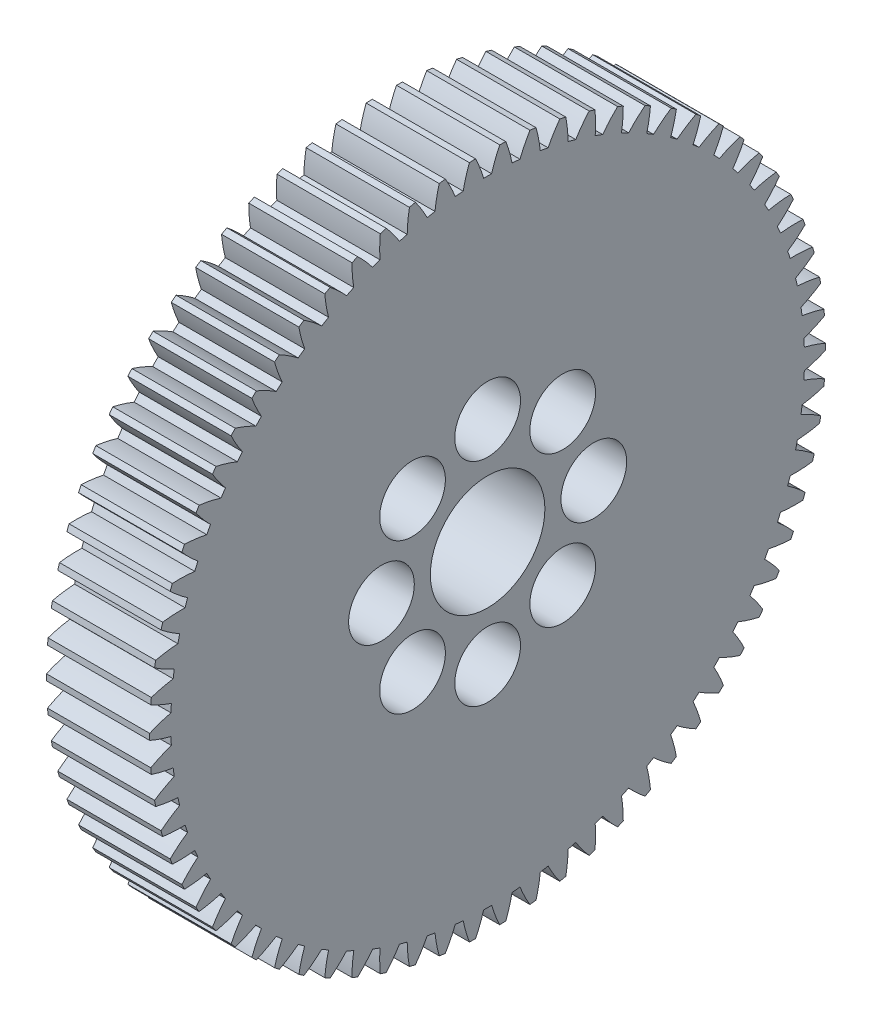
SolidWorks part; units mm, degrees
ref_plane "正面" through (0, 0, 0) normal (0, 0, 1) x (1, 0, 0)
ref_plane "平面" through (0, 0, 0) normal (0, 1, 0) x (1, 0, 0)
ref_plane "右側面" through (0, 0, 0) normal (1, 0, 0) x (0, 0, -1)
ref_plane "Plane1" through (10.108, 0, 0) normal (1, 0, 0) x (0, 0, -1)
sketch "Sketch1" plane through (10.108, 0, 0) normal (1, 0, 0) x (0, 0, -1)
  circle A0 centre (0, -2.0042) radius 4
  arc A1 (-32.5754, 13.3205) -> (-30.8638, 11.6495) centre (-21.9753, 22.466) ccw
  arc A2 (-30.8638, 11.6495) -> (-31.1976, 10.8685) centre (0, -2.0042) ccw
  arc A3 (-31.1976, 10.8685) -> (-33.5882, 10.9508) centre (-32.8732, -3.0309) ccw
  arc A4 (-33.5882, 10.9508) -> (-33.8179, 10.3388) centre (0, -2.0042) ccw
  arc A5 (-33.8179, 10.3388) -> (-31.9634, 8.8279) centre (-24.0803, 20.3976) ccw
  arc A6 (-31.9634, 8.8279) -> (-32.2259, 8.0201) centre (0, -2.0042) ccw
  arc A7 (-32.2259, 8.0201) -> (-34.6143, 7.8879) centre (-32.6488, -5.9735) ccw
  arc A8 (-34.6143, 7.8879) -> (-34.7882, 7.2577) centre (0, -2.0042) ccw
  arc A9 (-34.7882, 7.2577) -> (-32.8057, 5.9191) centre (-25.9915, 18.1489) ccw
  arc A10 (-32.8057, 5.9191) -> (-32.9947, 5.0911) centre (0, -2.0042) ccw
  arc A11 (-32.9947, 5.0911) -> (-35.3616, 4.7452) centre (-32.1616, -8.8841) ccw
  arc A12 (-35.3616, 4.7452) -> (-35.4784, 4.102) centre (0, -2.0042) ccw
  arc A13 (-35.4784, 4.102) -> (-33.3839, 2.9466) centre (-27.6934, 15.7379) ccw
  arc A14 (-33.3839, 2.9466) -> (-33.4979, 2.1049) centre (0, -2.0042) ccw
  arc A15 (-33.4979, 2.1049) -> (-35.8243, 1.5483) centre (-31.4154, -11.7394) ccw
  arc A16 (-35.8243, 1.5483) -> (-35.8829, 0.8972) centre (0, -2.0042) ccw
  arc A17 (-35.8829, 0.8972) -> (-33.6933, -0.0659) centre (-29.1723, 13.184) ccw
  arc A18 (-33.6933, -0.0659) -> (-33.7314, -0.9144) centre (0, -2.0042) ccw
  arc A19 (-33.7314, -0.9144) -> (-35.9985, -1.6773) centre (-30.4163, -14.5162) ccw
  arc A20 (-35.9985, -1.6773) -> (-35.9985, -2.331) centre (0, -2.0042) ccw
  arc A21 (-35.9985, -2.331) -> (-33.7314, -3.0939) centre (-30.4163, 10.5079) ccw
  arc A22 (-33.7314, -3.0939) -> (-33.6933, -3.9425) centre (0, -2.0042) ccw
  arc A23 (-33.6933, -3.9425) -> (-35.8829, -4.9055) centre (-29.1723, -17.1924) ccw
  arc A24 (-35.8829, -4.9055) -> (-35.8243, -5.5566) centre (0, -2.0042) ccw
  arc A25 (-35.8243, -5.5566) -> (-33.4979, -6.1132) centre (-31.4154, 7.7311) ccw
  arc A26 (-33.4979, -6.1132) -> (-33.3839, -6.9549) centre (0, -2.0042) ccw
  arc A27 (-33.3839, -6.9549) -> (-35.4784, -8.1103) centre (-27.6934, -19.7462) ccw
  arc A28 (-35.4784, -8.1103) -> (-35.3616, -8.7536) centre (0, -2.0042) ccw
  arc A29 (-35.3616, -8.7536) -> (-32.9947, -9.0994) centre (-32.1616, 4.8758) ccw
  arc A30 (-32.9947, -9.0994) -> (-32.8057, -9.9275) centre (0, -2.0042) ccw
  arc A31 (-32.8057, -9.9275) -> (-34.7882, -11.266) centre (-25.9915, -22.1572) ccw
  arc A32 (-34.7882, -11.266) -> (-34.6143, -11.8962) centre (0, -2.0042) ccw
  arc A33 (-34.6143, -11.8962) -> (-32.2259, -12.0284) centre (-32.6488, 1.9652) ccw
  arc A34 (-32.2259, -12.0284) -> (-31.9634, -12.8363) centre (0, -2.0042) ccw
  arc A35 (-31.9634, -12.8363) -> (-33.8179, -14.3471) centre (-24.0803, -24.4059) ccw
  arc A36 (-33.8179, -14.3471) -> (-33.5882, -14.9592) centre (0, -2.0042) ccw
  arc A37 (-33.5882, -14.9592) -> (-31.1976, -14.8768) centre (-32.8732, -0.9774) ccw
  arc A38 (-31.1976, -14.8768) -> (-30.8638, -15.6578) centre (0, -2.0042) ccw
  arc A39 (-30.8638, -15.6578) -> (-32.5754, -17.3288) centre (-21.9753, -26.4743) ccw
  arc A40 (-32.5754, -17.3288) -> (-32.2917, -17.9178) centre (0, -2.0042) ccw
  arc A41 (-32.2917, -17.9178) -> (-29.9181, -17.6215) centre (-32.8329, -3.9283) ccw
  arc A42 (-29.9181, -17.6215) -> (-29.5156, -18.3695) centre (0, -2.0042) ccw
  arc A43 (-29.5156, -18.3695) -> (-31.0705, -20.1872) centre (-19.6934, -28.3456) ccw
  arc A44 (-31.0705, -20.1872) -> (-30.7352, -20.7484) centre (0, -2.0042) ccw
  arc A45 (-30.7352, -20.7484) -> (-28.3977, -20.2405) centre (-32.5283, -6.8637) ccw
  arc A46 (-28.3977, -20.2405) -> (-27.9298, -20.9494) centre (0, -2.0042) ccw
  arc A47 (-27.9298, -20.9494) -> (-29.3155, -22.8991) centre (-17.2529, -30.0049) ccw
  arc A48 (-29.3155, -22.8991) -> (-28.9313, -23.428) centre (0, -2.0042) ccw
  arc A49 (-28.9313, -23.428) -> (-26.6487, -22.7126) centre (-31.9617, -9.7599) ccw
  arc A50 (-26.6487, -22.7126) -> (-26.1191, -23.3767) centre (0, -2.0042) ccw
  arc A51 (-26.1191, -23.3767) -> (-27.3245, -25.4428) centre (-14.6734, -31.4387) ccw
  arc A52 (-27.3245, -25.4428) -> (-26.8944, -25.9351) centre (0, -2.0042) ccw
  arc A53 (-26.8944, -25.9351) -> (-24.6852, -25.018) centre (-31.1378, -12.5937) ccw
  arc A54 (-24.6852, -25.018) -> (-24.0982, -25.632) centre (0, -2.0042) ccw
  arc A55 (-24.0982, -25.632) -> (-25.1135, -27.7978) centre (-11.9759, -32.6355) ccw
  arc A56 (-25.1135, -27.7978) -> (-24.641, -28.2496) centre (0, -2.0042) ccw
  arc A57 (-24.641, -28.2496) -> (-22.5228, -27.1381) centre (-30.0632, -15.3423) ccw
  arc A58 (-22.5228, -27.1381) -> (-21.8832, -27.697) centre (0, -2.0042) ccw
  arc A59 (-21.8832, -27.697) -> (-22.7003, -29.9451) centre (-9.1819, -33.5857) ccw
  arc A60 (-22.7003, -29.9451) -> (-22.1892, -30.3527) centre (0, -2.0042) ccw
  arc A61 (-22.1892, -30.3527) -> (-20.1792, -29.0559) centre (-28.7466, -17.9834) ccw
  arc A62 (-20.1792, -29.0559) -> (-19.492, -29.5551) centre (0, -2.0042) ccw
  arc A63 (-19.492, -29.5551) -> (-20.1043, -31.8675) centre (-6.314, -34.2816) ccw
  arc A64 (-20.1043, -31.8675) -> (-19.5587, -32.2276) centre (0, -2.0042) ccw
  arc A65 (-19.5587, -32.2276) -> (-17.673, -30.7558) centre (-27.1985, -20.4959) ccw
  arc A66 (-17.673, -30.7558) -> (-16.9439, -31.1915) centre (0, -2.0042) ccw
  arc A67 (-16.9439, -31.1915) -> (-17.3464, -33.5494) centre (-3.3952, -34.7177) ccw
  arc A68 (-17.3464, -33.5494) -> (-16.7707, -33.8592) centre (0, -2.0042) ccw
  arc A69 (-16.7707, -33.8592) -> (-15.0246, -32.2243) centre (-25.4314, -22.8595) ccw
  arc A70 (-15.0246, -32.2243) -> (-14.2593, -32.5928) centre (0, -2.0042) ccw
  arc A71 (-14.2593, -32.5928) -> (-14.4489, -34.9773) centre (-0.4492, -34.8903) ccw
  arc A72 (-14.4489, -34.9773) -> (-13.8478, -35.2343) centre (0, -2.0042) ccw
  arc A73 (-13.8478, -35.2343) -> (-12.2552, -33.4494) centre (-23.4596, -25.0552) ccw
  arc A74 (-12.2552, -33.4494) -> (-11.46, -33.7479) centre (0, -2.0042) ccw
  arc A75 (-11.46, -33.7479) -> (-11.435, -36.1398) centre (2.5006, -34.7982) ccw
  arc A76 (-11.435, -36.1398) -> (-10.8133, -36.3418) centre (0, -2.0042) ccw
  arc A77 (-10.8133, -36.3418) -> (-9.3872, -34.4214) centre (-21.2988, -27.0653) ccw
  arc A78 (-9.3872, -34.4214) -> (-8.5684, -34.6474) centre (0, -2.0042) ccw
  arc A79 (-8.5684, -34.6474) -> (-8.3291, -37.0274) centre (5.4301, -34.442) ccw
  arc A80 (-8.3291, -37.0274) -> (-7.6918, -37.1729) centre (0, -2.0042) ccw
  arc A81 (-7.6918, -37.1729) -> (-6.4435, -35.1323) centre (-18.9666, -28.8736) ccw
  arc A82 (-6.4435, -35.1323) -> (-5.6078, -35.284) centre (0, -2.0042) ccw
  arc A83 (-5.6078, -35.284) -> (-5.1561, -37.633) centre (8.316, -33.8247) ccw
  arc A84 (-5.1561, -37.633) -> (-4.5083, -37.7208) centre (0, -2.0042) ccw
  arc A85 (-4.5083, -37.7208) -> (-3.448, -35.5766) centre (-16.4817, -30.4656) ccw
  arc A86 (-3.448, -35.5766) -> (-2.602, -35.6527) centre (0, -2.0042) ccw
  arc A87 (-2.602, -35.6527) -> (-1.9416, -37.9518) centre (11.1349, -32.9512) ccw
  arc A88 (-1.9416, -37.9518) -> (-1.2885, -37.9811) centre (0, -2.0042) ccw
  arc A89 (-1.2885, -37.9811) -> (-0.4247, -35.7505) centre (-13.8641, -31.8285) ccw
  arc A90 (-0.4247, -35.7505) -> (0.4247, -35.7505) centre (0, -2.0042) ccw
  arc A91 (0.4247, -35.7505) -> (1.2885, -37.9811) centre (13.8641, -31.8285) ccw
  arc A92 (1.2885, -37.9811) -> (1.9416, -37.9518) centre (0, -2.0042) ccw
  arc A93 (1.9416, -37.9518) -> (2.602, -35.6527) centre (-11.1349, -32.9512) ccw
  arc A94 (2.602, -35.6527) -> (3.448, -35.5766) centre (0, -2.0042) ccw
  arc A95 (3.448, -35.5766) -> (4.5083, -37.7208) centre (16.4817, -30.4656) ccw
  arc A96 (4.5083, -37.7208) -> (5.1561, -37.633) centre (0, -2.0042) ccw
  arc A97 (5.1561, -37.633) -> (5.6078, -35.284) centre (-8.316, -33.8247) ccw
  arc A98 (5.6078, -35.284) -> (6.4435, -35.1323) centre (0, -2.0042) ccw
  arc A99 (6.4435, -35.1323) -> (7.6918, -37.1729) centre (18.9666, -28.8736) ccw
  arc A100 (7.6918, -37.1729) -> (8.3291, -37.0274) centre (0, -2.0042) ccw
  arc A101 (8.3291, -37.0274) -> (8.5684, -34.6474) centre (-5.4301, -34.442) ccw
  arc A102 (8.5684, -34.6474) -> (9.3872, -34.4214) centre (0, -2.0042) ccw
  arc A103 (9.3872, -34.4214) -> (10.8133, -36.3418) centre (21.2988, -27.0653) ccw
  arc A104 (10.8133, -36.3418) -> (11.435, -36.1398) centre (0, -2.0042) ccw
  arc A105 (11.435, -36.1398) -> (11.46, -33.7479) centre (-2.5006, -34.7982) ccw
  arc A106 (11.46, -33.7479) -> (12.2552, -33.4494) centre (0, -2.0042) ccw
  arc A107 (12.2552, -33.4494) -> (13.8478, -35.2343) centre (23.4596, -25.0552) ccw
  arc A108 (13.8478, -35.2343) -> (14.4489, -34.9773) centre (0, -2.0042) ccw
  arc A109 (14.4489, -34.9773) -> (14.2593, -32.5928) centre (0.4492, -34.8903) ccw
  arc A110 (14.2593, -32.5928) -> (15.0246, -32.2243) centre (0, -2.0042) ccw
  arc A111 (15.0246, -32.2243) -> (16.7707, -33.8592) centre (25.4314, -22.8595) ccw
  arc A112 (16.7707, -33.8592) -> (17.3464, -33.5494) centre (0, -2.0042) ccw
  arc A113 (17.3464, -33.5494) -> (16.9439, -31.1915) centre (3.3952, -34.7177) ccw
  arc A114 (16.9439, -31.1915) -> (17.673, -30.7558) centre (0, -2.0042) ccw
  arc A115 (17.673, -30.7558) -> (19.5587, -32.2276) centre (27.1985, -20.4959) ccw
  arc A116 (19.5587, -32.2276) -> (20.1043, -31.8675) centre (0, -2.0042) ccw
  arc A117 (20.1043, -31.8675) -> (19.492, -29.5551) centre (6.314, -34.2816) ccw
  arc A118 (19.492, -29.5551) -> (20.1792, -29.0559) centre (0, -2.0042) ccw
  arc A119 (20.1792, -29.0559) -> (22.1892, -30.3527) centre (28.7466, -17.9834) ccw
  arc A120 (22.1892, -30.3527) -> (22.7003, -29.9451) centre (0, -2.0042) ccw
  arc A121 (22.7003, -29.9451) -> (21.8832, -27.697) centre (9.1819, -33.5857) ccw
  arc A122 (21.8832, -27.697) -> (22.5228, -27.1381) centre (0, -2.0042) ccw
  arc A123 (22.5228, -27.1381) -> (24.641, -28.2496) centre (30.0632, -15.3423) ccw
  arc A124 (24.641, -28.2496) -> (25.1135, -27.7978) centre (0, -2.0042) ccw
  arc A125 (25.1135, -27.7978) -> (24.0982, -25.632) centre (11.9759, -32.6355) ccw
  arc A126 (24.0982, -25.632) -> (24.6852, -25.018) centre (0, -2.0042) ccw
  arc A127 (24.6852, -25.018) -> (26.8944, -25.9351) centre (31.1378, -12.5937) ccw
  arc A128 (26.8944, -25.9351) -> (27.3245, -25.4428) centre (0, -2.0042) ccw
  arc A129 (27.3245, -25.4428) -> (26.1191, -23.3767) centre (14.6734, -31.4387) ccw
  arc A130 (26.1191, -23.3767) -> (26.6487, -22.7126) centre (0, -2.0042) ccw
  arc A131 (26.6487, -22.7126) -> (28.9313, -23.428) centre (31.9617, -9.7599) ccw
  arc A132 (28.9313, -23.428) -> (29.3155, -22.8991) centre (0, -2.0042) ccw
  arc A133 (29.3155, -22.8991) -> (27.9298, -20.9494) centre (17.2529, -30.0049) ccw
  arc A134 (27.9298, -20.9494) -> (28.3977, -20.2405) centre (0, -2.0042) ccw
  arc A135 (28.3977, -20.2405) -> (30.7352, -20.7484) centre (32.5283, -6.8637) ccw
  arc A136 (30.7352, -20.7484) -> (31.0705, -20.1872) centre (0, -2.0042) ccw
  arc A137 (31.0705, -20.1872) -> (29.5156, -18.3695) centre (19.6934, -28.3456) ccw
  arc A138 (29.5156, -18.3695) -> (29.9181, -17.6215) centre (0, -2.0042) ccw
  arc A139 (29.9181, -17.6215) -> (32.2917, -17.9178) centre (32.8329, -3.9283) ccw
  arc A140 (32.2917, -17.9178) -> (32.5754, -17.3288) centre (0, -2.0042) ccw
  arc A141 (32.5754, -17.3288) -> (30.8638, -15.6578) centre (21.9753, -26.4743) ccw
  arc A142 (30.8638, -15.6578) -> (31.1976, -14.8768) centre (0, -2.0042) ccw
  arc A143 (31.1976, -14.8768) -> (33.5882, -14.9592) centre (32.8732, -0.9774) ccw
  arc A144 (33.5882, -14.9592) -> (33.8179, -14.3471) centre (0, -2.0042) ccw
  arc A145 (33.8179, -14.3471) -> (31.9634, -12.8363) centre (24.0803, -24.4059) ccw
  arc A146 (31.9634, -12.8363) -> (32.2259, -12.0284) centre (0, -2.0042) ccw
  arc A147 (32.2259, -12.0284) -> (34.6143, -11.8962) centre (32.6488, 1.9652) ccw
  arc A148 (34.6143, -11.8962) -> (34.7882, -11.266) centre (0, -2.0042) ccw
  arc A149 (34.7882, -11.266) -> (32.8057, -9.9275) centre (25.9915, -22.1572) ccw
  arc A150 (32.8057, -9.9275) -> (32.9947, -9.0994) centre (0, -2.0042) ccw
  arc A151 (32.9947, -9.0994) -> (35.3616, -8.7536) centre (32.1616, 4.8758) ccw
  arc A152 (35.3616, -8.7536) -> (35.4784, -8.1103) centre (0, -2.0042) ccw
  arc A153 (35.4784, -8.1103) -> (33.3839, -6.9549) centre (27.6934, -19.7462) ccw
  arc A154 (33.3839, -6.9549) -> (33.4979, -6.1132) centre (0, -2.0042) ccw
  arc A155 (33.4979, -6.1132) -> (35.8243, -5.5566) centre (31.4154, 7.7311) ccw
  arc A156 (35.8243, -5.5566) -> (35.8829, -4.9055) centre (0, -2.0042) ccw
  arc A157 (35.8829, -4.9055) -> (33.6933, -3.9425) centre (29.1723, -17.1924) ccw
  arc A158 (33.6933, -3.9425) -> (33.7314, -3.0939) centre (0, -2.0042) ccw
  arc A159 (33.7314, -3.0939) -> (35.9985, -2.331) centre (30.4163, 10.5079) ccw
  arc A160 (35.9985, -2.331) -> (35.9985, -1.6773) centre (0, -2.0042) ccw
  arc A161 (35.9985, -1.6773) -> (33.7314, -0.9144) centre (30.4163, -14.5162) ccw
  arc A162 (33.7314, -0.9144) -> (33.6933, -0.0659) centre (0, -2.0042) ccw
  arc A163 (33.6933, -0.0659) -> (35.8829, 0.8972) centre (29.1723, 13.184) ccw
  arc A164 (35.8829, 0.8972) -> (35.8243, 1.5483) centre (0, -2.0042) ccw
  arc A165 (35.8243, 1.5483) -> (33.4979, 2.1049) centre (31.4154, -11.7394) ccw
  arc A166 (33.4979, 2.1049) -> (33.3839, 2.9466) centre (0, -2.0042) ccw
  arc A167 (33.3839, 2.9466) -> (35.4784, 4.102) centre (27.6934, 15.7379) ccw
  arc A168 (35.4784, 4.102) -> (35.3616, 4.7452) centre (0, -2.0042) ccw
  arc A169 (35.3616, 4.7452) -> (32.9947, 5.0911) centre (32.1616, -8.8841) ccw
  arc A170 (32.9947, 5.0911) -> (32.8057, 5.9191) centre (0, -2.0042) ccw
  arc A171 (32.8057, 5.9191) -> (34.7882, 7.2577) centre (25.9915, 18.1489) ccw
  arc A172 (34.7882, 7.2577) -> (34.6143, 7.8879) centre (0, -2.0042) ccw
  arc A173 (34.6143, 7.8879) -> (32.2259, 8.0201) centre (32.6488, -5.9735) ccw
  arc A174 (32.2259, 8.0201) -> (31.9634, 8.8279) centre (0, -2.0042) ccw
  arc A175 (31.9634, 8.8279) -> (33.8179, 10.3388) centre (24.0803, 20.3976) ccw
  arc A176 (33.8179, 10.3388) -> (33.5882, 10.9508) centre (0, -2.0042) ccw
  arc A177 (33.5882, 10.9508) -> (31.1976, 10.8685) centre (32.8732, -3.0309) ccw
  arc A178 (31.1976, 10.8685) -> (30.8638, 11.6495) centre (0, -2.0042) ccw
  arc A179 (30.8638, 11.6495) -> (32.5754, 13.3205) centre (21.9753, 22.466) ccw
  arc A180 (32.5754, 13.3205) -> (32.2917, 13.9095) centre (0, -2.0042) ccw
  arc A181 (32.2917, 13.9095) -> (29.9181, 13.6132) centre (32.8329, -0.08) ccw
  arc A182 (29.9181, 13.6132) -> (29.5156, 14.3611) centre (0, -2.0042) ccw
  arc A183 (29.5156, 14.3611) -> (31.0705, 16.1789) centre (19.6934, 24.3373) ccw
  arc A184 (31.0705, 16.1789) -> (30.7352, 16.74) centre (0, -2.0042) ccw
  arc A185 (30.7352, 16.74) -> (28.3977, 16.2321) centre (32.5283, 2.8553) ccw
  arc A186 (28.3977, 16.2321) -> (27.9298, 16.941) centre (0, -2.0042) ccw
  arc A187 (27.9298, 16.941) -> (29.3155, 18.8908) centre (17.2529, 25.9966) ccw
  arc A188 (29.3155, 18.8908) -> (28.9313, 19.4197) centre (0, -2.0042) ccw
  arc A189 (28.9313, 19.4197) -> (26.6487, 18.7043) centre (31.9617, 5.7516) ccw
  arc A190 (26.6487, 18.7043) -> (26.1191, 19.3684) centre (0, -2.0042) ccw
  arc A191 (26.1191, 19.3684) -> (27.3245, 21.4345) centre (14.6734, 27.4304) ccw
  arc A192 (27.3245, 21.4345) -> (26.8944, 21.9268) centre (0, -2.0042) ccw
  arc A193 (26.8944, 21.9268) -> (24.6852, 21.0097) centre (31.1378, 8.5854) ccw
  arc A194 (24.6852, 21.0097) -> (24.0982, 21.6236) centre (0, -2.0042) ccw
  arc A195 (24.0982, 21.6236) -> (25.1135, 23.7895) centre (11.9759, 28.6272) ccw
  arc A196 (25.1135, 23.7895) -> (24.641, 24.2413) centre (0, -2.0042) ccw
  arc A197 (24.641, 24.2413) -> (22.5228, 23.1298) centre (30.0632, 11.3339) ccw
  arc A198 (22.5228, 23.1298) -> (21.8832, 23.6887) centre (0, -2.0042) ccw
  arc A199 (21.8832, 23.6887) -> (22.7003, 25.9368) centre (9.1819, 29.5774) ccw
  arc A200 (22.7003, 25.9368) -> (22.1892, 26.3444) centre (0, -2.0042) ccw
  arc A201 (22.1892, 26.3444) -> (20.1792, 25.0476) centre (28.7466, 13.9751) ccw
  arc A202 (20.1792, 25.0476) -> (19.492, 25.5468) centre (0, -2.0042) ccw
  arc A203 (19.492, 25.5468) -> (20.1043, 27.8592) centre (6.314, 30.2733) ccw
  arc A204 (20.1043, 27.8592) -> (19.5587, 28.2193) centre (0, -2.0042) ccw
  arc A205 (19.5587, 28.2193) -> (17.673, 26.7475) centre (27.1985, 16.4876) ccw
  arc A206 (17.673, 26.7475) -> (16.9439, 27.1832) centre (0, -2.0042) ccw
  arc A207 (16.9439, 27.1832) -> (17.3464, 29.5411) centre (3.3952, 30.7094) ccw
  arc A208 (17.3464, 29.5411) -> (16.7707, 29.8509) centre (0, -2.0042) ccw
  arc A209 (16.7707, 29.8509) -> (15.0246, 28.216) centre (25.4314, 18.8512) ccw
  arc A210 (15.0246, 28.216) -> (14.2593, 28.5845) centre (0, -2.0042) ccw
  arc A211 (14.2593, 28.5845) -> (14.4489, 30.969) centre (0.4492, 30.882) ccw
  arc A212 (14.4489, 30.969) -> (13.8478, 31.2259) centre (0, -2.0042) ccw
  arc A213 (13.8478, 31.2259) -> (12.2552, 29.4411) centre (23.4596, 21.0469) ccw
  arc A214 (12.2552, 29.4411) -> (11.46, 29.7396) centre (0, -2.0042) ccw
  arc A215 (11.46, 29.7396) -> (11.435, 32.1315) centre (-2.5006, 30.7899) ccw
  arc A216 (11.435, 32.1315) -> (10.8133, 32.3335) centre (0, -2.0042) ccw
  arc A217 (10.8133, 32.3335) -> (9.3872, 30.4131) centre (21.2988, 23.057) ccw
  arc A218 (9.3872, 30.4131) -> (8.5684, 30.639) centre (0, -2.0042) ccw
  arc A219 (8.5684, 30.639) -> (8.3291, 33.0191) centre (-5.4301, 30.4337) ccw
  arc A220 (8.3291, 33.0191) -> (7.6918, 33.1645) centre (0, -2.0042) ccw
  arc A221 (7.6918, 33.1645) -> (6.4435, 31.124) centre (18.9666, 24.8653) ccw
  arc A222 (6.4435, 31.124) -> (5.6078, 31.2757) centre (0, -2.0042) ccw
  arc A223 (5.6078, 31.2757) -> (5.1561, 33.6247) centre (-8.316, 29.8164) ccw
  arc A224 (5.1561, 33.6247) -> (4.5083, 33.7124) centre (0, -2.0042) ccw
  arc A225 (4.5083, 33.7124) -> (3.448, 31.5682) centre (16.4817, 26.4573) ccw
  arc A226 (3.448, 31.5682) -> (2.602, 31.6444) centre (0, -2.0042) ccw
  arc A227 (2.602, 31.6444) -> (1.9416, 33.9434) centre (-11.1349, 28.9428) ccw
  arc A228 (1.9416, 33.9434) -> (1.2885, 33.9728) centre (0, -2.0042) ccw
  arc A229 (1.2885, 33.9728) -> (0.4247, 31.7422) centre (13.8641, 27.8201) ccw
  arc A230 (0.4247, 31.7422) -> (-0.4247, 31.7422) centre (0, -2.0042) ccw
  arc A231 (-0.4247, 31.7422) -> (-1.2885, 33.9728) centre (-13.8641, 27.8201) ccw
  arc A232 (-1.2885, 33.9728) -> (-1.9416, 33.9434) centre (0, -2.0042) ccw
  arc A233 (-1.9416, 33.9434) -> (-2.602, 31.6444) centre (11.1349, 28.9428) ccw
  arc A234 (-2.602, 31.6444) -> (-3.448, 31.5682) centre (0, -2.0042) ccw
  arc A235 (-3.448, 31.5682) -> (-4.5083, 33.7124) centre (-16.4817, 26.4573) ccw
  arc A236 (-4.5083, 33.7124) -> (-5.1561, 33.6247) centre (0, -2.0042) ccw
  arc A237 (-5.1561, 33.6247) -> (-5.6078, 31.2757) centre (8.316, 29.8164) ccw
  arc A238 (-5.6078, 31.2757) -> (-6.4435, 31.124) centre (0, -2.0042) ccw
  arc A239 (-6.4435, 31.124) -> (-7.6918, 33.1645) centre (-18.9666, 24.8653) ccw
  arc A240 (-7.6918, 33.1645) -> (-8.3291, 33.0191) centre (0, -2.0042) ccw
  arc A241 (-8.3291, 33.0191) -> (-8.5684, 30.639) centre (5.4301, 30.4337) ccw
  arc A242 (-8.5684, 30.639) -> (-9.3872, 30.4131) centre (0, -2.0042) ccw
  arc A243 (-9.3872, 30.4131) -> (-10.8133, 32.3335) centre (-21.2988, 23.057) ccw
  arc A244 (-10.8133, 32.3335) -> (-11.435, 32.1315) centre (0, -2.0042) ccw
  arc A245 (-11.435, 32.1315) -> (-11.46, 29.7396) centre (2.5006, 30.7899) ccw
  arc A246 (-11.46, 29.7396) -> (-12.2552, 29.4411) centre (0, -2.0042) ccw
  arc A247 (-12.2552, 29.4411) -> (-13.8478, 31.2259) centre (-23.4596, 21.0469) ccw
  arc A248 (-13.8478, 31.2259) -> (-14.4489, 30.969) centre (0, -2.0042) ccw
  arc A249 (-14.4489, 30.969) -> (-14.2593, 28.5845) centre (-0.4492, 30.882) ccw
  arc A250 (-14.2593, 28.5845) -> (-15.0246, 28.216) centre (0, -2.0042) ccw
  arc A251 (-15.0246, 28.216) -> (-16.7707, 29.8509) centre (-25.4314, 18.8512) ccw
  arc A252 (-16.7707, 29.8509) -> (-17.3464, 29.5411) centre (0, -2.0042) ccw
  arc A253 (-17.3464, 29.5411) -> (-16.9439, 27.1832) centre (-3.3952, 30.7094) ccw
  arc A254 (-16.9439, 27.1832) -> (-17.673, 26.7475) centre (0, -2.0042) ccw
  arc A255 (-17.673, 26.7475) -> (-19.5587, 28.2193) centre (-27.1985, 16.4876) ccw
  arc A256 (-19.5587, 28.2193) -> (-20.1043, 27.8592) centre (0, -2.0042) ccw
  arc A257 (-20.1043, 27.8592) -> (-19.492, 25.5468) centre (-6.314, 30.2733) ccw
  arc A258 (-19.492, 25.5468) -> (-20.1792, 25.0476) centre (0, -2.0042) ccw
  arc A259 (-20.1792, 25.0476) -> (-22.1892, 26.3444) centre (-28.7466, 13.9751) ccw
  arc A260 (-22.1892, 26.3444) -> (-22.7003, 25.9368) centre (0, -2.0042) ccw
  arc A261 (-22.7003, 25.9368) -> (-21.8832, 23.6887) centre (-9.1819, 29.5774) ccw
  arc A262 (-21.8832, 23.6887) -> (-22.5228, 23.1298) centre (0, -2.0042) ccw
  arc A263 (-22.5228, 23.1298) -> (-24.641, 24.2413) centre (-30.0632, 11.3339) ccw
  arc A264 (-24.641, 24.2413) -> (-25.1135, 23.7895) centre (0, -2.0042) ccw
  arc A265 (-25.1135, 23.7895) -> (-24.0982, 21.6236) centre (-11.9759, 28.6272) ccw
  arc A266 (-24.0982, 21.6236) -> (-24.6852, 21.0097) centre (0, -2.0042) ccw
  arc A267 (-24.6852, 21.0097) -> (-26.8944, 21.9268) centre (-31.1378, 8.5854) ccw
  arc A268 (-26.8944, 21.9268) -> (-27.3245, 21.4345) centre (0, -2.0042) ccw
  arc A269 (-27.3245, 21.4345) -> (-26.1191, 19.3684) centre (-14.6734, 27.4304) ccw
  arc A270 (-26.1191, 19.3684) -> (-26.6487, 18.7043) centre (0, -2.0042) ccw
  arc A271 (-26.6487, 18.7043) -> (-28.9313, 19.4197) centre (-31.9617, 5.7516) ccw
  arc A272 (-28.9313, 19.4197) -> (-29.3155, 18.8908) centre (0, -2.0042) ccw
  arc A273 (-29.3155, 18.8908) -> (-27.9298, 16.941) centre (-17.2529, 25.9966) ccw
  arc A274 (-27.9298, 16.941) -> (-28.3977, 16.2321) centre (0, -2.0042) ccw
  arc A275 (-28.3977, 16.2321) -> (-30.7352, 16.74) centre (-32.5283, 2.8553) ccw
  arc A276 (-30.7352, 16.74) -> (-31.0705, 16.1789) centre (0, -2.0042) ccw
  arc A277 (-31.0705, 16.1789) -> (-29.5156, 14.3611) centre (-19.6934, 24.3373) ccw
  arc A278 (-29.5156, 14.3611) -> (-29.9181, 13.6132) centre (0, -2.0042) ccw
  arc A279 (-29.9181, 13.6132) -> (-32.2917, 13.9095) centre (-32.8329, -0.08) ccw
  arc A280 (-32.2917, 13.9095) -> (-32.5754, 13.3205) centre (0, -2.0042) ccw
extrude "Boss-Extrude1" add sketch "Sketch1" against normal blind 6
sketch "Sketch2" plane through (4.108, 0, 0) normal (-1, 0, 0) x (0, 0, 1)
  circle A0 centre (0, -2.0042) radius 16
extrude "Boss-Extrude2" add sketch "Sketch2" along normal blind 12
sketch "Sketch3" plane through (-7.892, 0, 0) normal (-1, 0, 0) x (0, 0, 1)
  circle A0 centre (0, -2.0042) radius 6.1
extrude "Cut-Extrude1" cut sketch "Sketch3" against normal up to next
sketch "Sketch4" plane through (-7.892, 0, 0) normal (-1, 0, 0) x (0, 0, 1)
  circle A0 centre (11.31, -2.0042) radius 2.1
  circle A1 centre (7.9974, -10.0015) radius 2.1
  circle A2 centre (0, -13.3142) radius 2.1
  circle A3 centre (-7.9974, -10.0015) radius 2.1
  circle A4 centre (-11.31, -2.0042) radius 2.1
  circle A5 centre (-7.9974, 5.9932) radius 2.1
  circle A6 centre (0, 9.3058) radius 2.1
  circle A7 centre (7.9974, 5.9932) radius 2.1
extrude "Cut-Extrude2" cut sketch "Sketch4" against normal up to next
sketch "Sketch5" plane through (10.108, 0, 0) normal (1, 0, 0) x (0, 0, -1)
  circle A0 centre (0, 9.3058) radius 3.5
  circle A1 centre (7.9974, 5.9932) radius 3.5
  circle A2 centre (11.31, -2.0042) radius 3.5
  circle A3 centre (7.9974, -10.0015) radius 3.5
  circle A4 centre (0, -13.3142) radius 3.5
  circle A5 centre (-7.9974, -10.0015) radius 3.5
  circle A6 centre (-11.31, -2.0042) radius 3.5
  circle A7 centre (-7.9974, 5.9932) radius 3.5
extrude "Cut-Extrude3" cut sketch "Sketch5" against normal blind 4
sketch "Sketch6" plane through (10.108, 0, 0) normal (1, 0, 0) x (0, 0, -1)
  circle A0 centre (0, -13.3142) radius 3.5
  circle A1 centre (7.9974, -10.0015) radius 3.5
  circle A2 centre (11.31, -2.0042) radius 3.5
  circle A3 centre (7.9974, 5.9932) radius 3.5
  circle A4 centre (0, 9.3058) radius 3.5
  circle A5 centre (-7.9974, 5.9932) radius 3.5
  circle A6 centre (-7.9974, -10.0015) radius 3.5
  circle A7 centre (-11.31, -2.0042) radius 3.5
  arc A8 (-32.5754, 13.3205) -> (-30.8638, 11.6495) centre (-21.9753, 22.466) ccw
  arc A9 (-30.8638, 11.6495) -> (-31.1976, 10.8685) centre (0, -2.0042) ccw
  arc A10 (-31.1976, 10.8685) -> (-33.5882, 10.9508) centre (-32.8732, -3.0309) ccw
  arc A11 (-33.5882, 10.9508) -> (-33.8179, 10.3388) centre (0, -2.0042) ccw
  arc A12 (-33.8179, 10.3388) -> (-31.9634, 8.8279) centre (-24.0803, 20.3976) ccw
  arc A13 (-31.9634, 8.8279) -> (-32.2259, 8.0201) centre (0, -2.0042) ccw
  arc A14 (-32.2259, 8.0201) -> (-34.6143, 7.8879) centre (-32.6488, -5.9735) ccw
  arc A15 (-34.6143, 7.8879) -> (-34.7882, 7.2577) centre (0, -2.0042) ccw
  arc A16 (-34.7882, 7.2577) -> (-32.8057, 5.9191) centre (-25.9915, 18.1489) ccw
  arc A17 (-32.8057, 5.9191) -> (-32.9947, 5.0911) centre (0, -2.0042) ccw
  arc A18 (-32.9947, 5.0911) -> (-35.3616, 4.7452) centre (-32.1616, -8.8841) ccw
  arc A19 (-35.3616, 4.7452) -> (-35.4784, 4.102) centre (0, -2.0042) ccw
  arc A20 (-35.4784, 4.102) -> (-33.3839, 2.9466) centre (-27.6934, 15.7379) ccw
  arc A21 (-33.3839, 2.9466) -> (-33.4979, 2.1049) centre (0, -2.0042) ccw
  arc A22 (-33.4979, 2.1049) -> (-35.8243, 1.5483) centre (-31.4154, -11.7394) ccw
  arc A23 (-35.8243, 1.5483) -> (-35.8829, 0.8972) centre (0, -2.0042) ccw
  arc A24 (-35.8829, 0.8972) -> (-33.6933, -0.0659) centre (-29.1723, 13.184) ccw
  arc A25 (-33.6933, -0.0659) -> (-33.7314, -0.9144) centre (0, -2.0042) ccw
  arc A26 (-33.7314, -0.9144) -> (-35.9985, -1.6773) centre (-30.4163, -14.5162) ccw
  arc A27 (-35.9985, -1.6773) -> (-35.9985, -2.331) centre (0, -2.0042) ccw
  arc A28 (-35.9985, -2.331) -> (-33.7314, -3.0939) centre (-30.4163, 10.5079) ccw
  arc A29 (-33.7314, -3.0939) -> (-33.6933, -3.9425) centre (0, -2.0042) ccw
  arc A30 (-33.6933, -3.9425) -> (-35.8829, -4.9055) centre (-29.1723, -17.1924) ccw
  arc A31 (-35.8829, -4.9055) -> (-35.8243, -5.5566) centre (0, -2.0042) ccw
  arc A32 (-35.8243, -5.5566) -> (-33.4979, -6.1132) centre (-31.4154, 7.7311) ccw
  arc A33 (-33.4979, -6.1132) -> (-33.3839, -6.9549) centre (0, -2.0042) ccw
  arc A34 (-33.3839, -6.9549) -> (-35.4784, -8.1103) centre (-27.6934, -19.7462) ccw
  arc A35 (-35.4784, -8.1103) -> (-35.3616, -8.7536) centre (0, -2.0042) ccw
  arc A36 (-35.3616, -8.7536) -> (-32.9947, -9.0994) centre (-32.1616, 4.8758) ccw
  arc A37 (-32.9947, -9.0994) -> (-32.8057, -9.9275) centre (0, -2.0042) ccw
  arc A38 (-32.8057, -9.9275) -> (-34.7882, -11.266) centre (-25.9915, -22.1572) ccw
  arc A39 (-34.7882, -11.266) -> (-34.6143, -11.8962) centre (0, -2.0042) ccw
  arc A40 (-34.6143, -11.8962) -> (-32.2259, -12.0284) centre (-32.6488, 1.9652) ccw
  arc A41 (-32.2259, -12.0284) -> (-31.9634, -12.8363) centre (0, -2.0042) ccw
  arc A42 (-31.9634, -12.8363) -> (-33.8179, -14.3471) centre (-24.0803, -24.4059) ccw
  arc A43 (-33.8179, -14.3471) -> (-33.5882, -14.9592) centre (0, -2.0042) ccw
  arc A44 (-33.5882, -14.9592) -> (-31.1976, -14.8768) centre (-32.8732, -0.9774) ccw
  arc A45 (-31.1976, -14.8768) -> (-30.8638, -15.6578) centre (0, -2.0042) ccw
  arc A46 (-30.8638, -15.6578) -> (-32.5754, -17.3288) centre (-21.9753, -26.4743) ccw
  arc A47 (-32.5754, -17.3288) -> (-32.2917, -17.9178) centre (0, -2.0042) ccw
  arc A48 (-32.2917, -17.9178) -> (-29.9181, -17.6215) centre (-32.8329, -3.9283) ccw
  arc A49 (-29.9181, -17.6215) -> (-29.5156, -18.3695) centre (0, -2.0042) ccw
  arc A50 (-29.5156, -18.3695) -> (-31.0705, -20.1872) centre (-19.6934, -28.3456) ccw
  arc A51 (-31.0705, -20.1872) -> (-30.7352, -20.7484) centre (0, -2.0042) ccw
  arc A52 (-30.7352, -20.7484) -> (-28.3977, -20.2405) centre (-32.5283, -6.8637) ccw
  arc A53 (-28.3977, -20.2405) -> (-27.9298, -20.9494) centre (0, -2.0042) ccw
  arc A54 (-27.9298, -20.9494) -> (-29.3155, -22.8991) centre (-17.2529, -30.0049) ccw
  arc A55 (-29.3155, -22.8991) -> (-28.9313, -23.428) centre (0, -2.0042) ccw
  arc A56 (-28.9313, -23.428) -> (-26.6487, -22.7126) centre (-31.9617, -9.7599) ccw
  arc A57 (-26.6487, -22.7126) -> (-26.1191, -23.3767) centre (0, -2.0042) ccw
  arc A58 (-26.1191, -23.3767) -> (-27.3245, -25.4428) centre (-14.6734, -31.4387) ccw
  arc A59 (-27.3245, -25.4428) -> (-26.8944, -25.9351) centre (0, -2.0042) ccw
  arc A60 (-26.8944, -25.9351) -> (-24.6852, -25.018) centre (-31.1378, -12.5937) ccw
  arc A61 (-24.6852, -25.018) -> (-24.0982, -25.632) centre (0, -2.0042) ccw
  arc A62 (-24.0982, -25.632) -> (-25.1135, -27.7978) centre (-11.9759, -32.6355) ccw
  arc A63 (-25.1135, -27.7978) -> (-24.641, -28.2496) centre (0, -2.0042) ccw
  arc A64 (-24.641, -28.2496) -> (-22.5228, -27.1381) centre (-30.0632, -15.3423) ccw
  arc A65 (-22.5228, -27.1381) -> (-21.8832, -27.697) centre (0, -2.0042) ccw
  arc A66 (-21.8832, -27.697) -> (-22.7003, -29.9451) centre (-9.1819, -33.5857) ccw
  arc A67 (-22.7003, -29.9451) -> (-22.1892, -30.3527) centre (0, -2.0042) ccw
  arc A68 (-22.1892, -30.3527) -> (-20.1792, -29.0559) centre (-28.7466, -17.9834) ccw
  arc A69 (-20.1792, -29.0559) -> (-19.492, -29.5551) centre (0, -2.0042) ccw
  arc A70 (-19.492, -29.5551) -> (-20.1043, -31.8675) centre (-6.314, -34.2816) ccw
  arc A71 (-20.1043, -31.8675) -> (-19.5587, -32.2276) centre (0, -2.0042) ccw
  arc A72 (-19.5587, -32.2276) -> (-17.673, -30.7558) centre (-27.1985, -20.4959) ccw
  arc A73 (-17.673, -30.7558) -> (-16.9439, -31.1915) centre (0, -2.0042) ccw
  arc A74 (-16.9439, -31.1915) -> (-17.3464, -33.5494) centre (-3.3952, -34.7177) ccw
  arc A75 (-17.3464, -33.5494) -> (-16.7707, -33.8592) centre (0, -2.0042) ccw
  arc A76 (-16.7707, -33.8592) -> (-15.0246, -32.2243) centre (-25.4314, -22.8595) ccw
  arc A77 (-15.0246, -32.2243) -> (-14.2593, -32.5928) centre (0, -2.0042) ccw
  arc A78 (-14.2593, -32.5928) -> (-14.4489, -34.9773) centre (-0.4492, -34.8903) ccw
  arc A79 (-14.4489, -34.9773) -> (-13.8478, -35.2343) centre (0, -2.0042) ccw
  arc A80 (-13.8478, -35.2343) -> (-12.2552, -33.4494) centre (-23.4596, -25.0552) ccw
  arc A81 (-12.2552, -33.4494) -> (-11.46, -33.7479) centre (0, -2.0042) ccw
  arc A82 (-11.46, -33.7479) -> (-11.435, -36.1398) centre (2.5006, -34.7982) ccw
  arc A83 (-11.435, -36.1398) -> (-10.8133, -36.3418) centre (0, -2.0042) ccw
  arc A84 (-10.8133, -36.3418) -> (-9.3872, -34.4214) centre (-21.2988, -27.0653) ccw
  arc A85 (-9.3872, -34.4214) -> (-8.5684, -34.6474) centre (0, -2.0042) ccw
  arc A86 (-8.5684, -34.6474) -> (-8.3291, -37.0274) centre (5.4301, -34.442) ccw
  arc A87 (-8.3291, -37.0274) -> (-7.6918, -37.1729) centre (0, -2.0042) ccw
  arc A88 (-7.6918, -37.1729) -> (-6.4435, -35.1323) centre (-18.9666, -28.8736) ccw
  arc A89 (-6.4435, -35.1323) -> (-5.6078, -35.284) centre (0, -2.0042) ccw
  arc A90 (-5.6078, -35.284) -> (-5.1561, -37.633) centre (8.316, -33.8247) ccw
  arc A91 (-5.1561, -37.633) -> (-4.5083, -37.7208) centre (0, -2.0042) ccw
  arc A92 (-4.5083, -37.7208) -> (-3.448, -35.5766) centre (-16.4817, -30.4656) ccw
  arc A93 (-3.448, -35.5766) -> (-2.602, -35.6527) centre (0, -2.0042) ccw
  arc A94 (-2.602, -35.6527) -> (-1.9416, -37.9518) centre (11.1349, -32.9512) ccw
  arc A95 (-1.9416, -37.9518) -> (-1.2885, -37.9811) centre (0, -2.0042) ccw
  arc A96 (-1.2885, -37.9811) -> (-0.4247, -35.7505) centre (-13.8641, -31.8285) ccw
  arc A97 (-0.4247, -35.7505) -> (0.4247, -35.7505) centre (0, -2.0042) ccw
  arc A98 (0.4247, -35.7505) -> (1.2885, -37.9811) centre (13.8641, -31.8285) ccw
  arc A99 (1.2885, -37.9811) -> (1.9416, -37.9518) centre (0, -2.0042) ccw
  arc A100 (1.9416, -37.9518) -> (2.602, -35.6527) centre (-11.1349, -32.9512) ccw
  arc A101 (2.602, -35.6527) -> (3.448, -35.5766) centre (0, -2.0042) ccw
  arc A102 (3.448, -35.5766) -> (4.5083, -37.7208) centre (16.4817, -30.4656) ccw
  arc A103 (4.5083, -37.7208) -> (5.1561, -37.633) centre (0, -2.0042) ccw
  arc A104 (5.1561, -37.633) -> (5.6078, -35.284) centre (-8.316, -33.8247) ccw
  arc A105 (5.6078, -35.284) -> (6.4435, -35.1323) centre (0, -2.0042) ccw
  arc A106 (6.4435, -35.1323) -> (7.6918, -37.1729) centre (18.9666, -28.8736) ccw
  arc A107 (7.6918, -37.1729) -> (8.3291, -37.0274) centre (0, -2.0042) ccw
  arc A108 (8.3291, -37.0274) -> (8.5684, -34.6474) centre (-5.4301, -34.442) ccw
  arc A109 (8.5684, -34.6474) -> (9.3872, -34.4214) centre (0, -2.0042) ccw
  arc A110 (9.3872, -34.4214) -> (10.8133, -36.3418) centre (21.2988, -27.0653) ccw
  arc A111 (10.8133, -36.3418) -> (11.435, -36.1398) centre (0, -2.0042) ccw
  arc A112 (11.435, -36.1398) -> (11.46, -33.7479) centre (-2.5006, -34.7982) ccw
  arc A113 (11.46, -33.7479) -> (12.2552, -33.4494) centre (0, -2.0042) ccw
  arc A114 (12.2552, -33.4494) -> (13.8478, -35.2343) centre (23.4596, -25.0552) ccw
  arc A115 (13.8478, -35.2343) -> (14.4489, -34.9773) centre (0, -2.0042) ccw
  arc A116 (14.4489, -34.9773) -> (14.2593, -32.5928) centre (0.4492, -34.8903) ccw
  arc A117 (14.2593, -32.5928) -> (15.0246, -32.2243) centre (0, -2.0042) ccw
  arc A118 (15.0246, -32.2243) -> (16.7707, -33.8592) centre (25.4314, -22.8595) ccw
  arc A119 (16.7707, -33.8592) -> (17.3464, -33.5494) centre (0, -2.0042) ccw
  arc A120 (17.3464, -33.5494) -> (16.9439, -31.1915) centre (3.3952, -34.7177) ccw
  arc A121 (16.9439, -31.1915) -> (17.673, -30.7558) centre (0, -2.0042) ccw
  arc A122 (17.673, -30.7558) -> (19.5587, -32.2276) centre (27.1985, -20.4959) ccw
  arc A123 (19.5587, -32.2276) -> (20.1043, -31.8675) centre (0, -2.0042) ccw
  arc A124 (20.1043, -31.8675) -> (19.492, -29.5551) centre (6.314, -34.2816) ccw
  arc A125 (19.492, -29.5551) -> (20.1792, -29.0559) centre (0, -2.0042) ccw
  arc A126 (20.1792, -29.0559) -> (22.1892, -30.3527) centre (28.7466, -17.9834) ccw
  arc A127 (22.1892, -30.3527) -> (22.7003, -29.9451) centre (0, -2.0042) ccw
  arc A128 (22.7003, -29.9451) -> (21.8832, -27.697) centre (9.1819, -33.5857) ccw
  arc A129 (21.8832, -27.697) -> (22.5228, -27.1381) centre (0, -2.0042) ccw
  arc A130 (22.5228, -27.1381) -> (24.641, -28.2496) centre (30.0632, -15.3423) ccw
  arc A131 (24.641, -28.2496) -> (25.1135, -27.7978) centre (0, -2.0042) ccw
  arc A132 (25.1135, -27.7978) -> (24.0982, -25.632) centre (11.9759, -32.6355) ccw
  arc A133 (24.0982, -25.632) -> (24.6852, -25.018) centre (0, -2.0042) ccw
  arc A134 (24.6852, -25.018) -> (26.8944, -25.9351) centre (31.1378, -12.5937) ccw
  arc A135 (26.8944, -25.9351) -> (27.3245, -25.4428) centre (0, -2.0042) ccw
  arc A136 (27.3245, -25.4428) -> (26.1191, -23.3767) centre (14.6734, -31.4387) ccw
  arc A137 (26.1191, -23.3767) -> (26.6487, -22.7126) centre (0, -2.0042) ccw
  arc A138 (26.6487, -22.7126) -> (28.9313, -23.428) centre (31.9617, -9.7599) ccw
  arc A139 (28.9313, -23.428) -> (29.3155, -22.8991) centre (0, -2.0042) ccw
  arc A140 (29.3155, -22.8991) -> (27.9298, -20.9494) centre (17.2529, -30.0049) ccw
  arc A141 (27.9298, -20.9494) -> (28.3977, -20.2405) centre (0, -2.0042) ccw
  arc A142 (28.3977, -20.2405) -> (30.7352, -20.7484) centre (32.5283, -6.8637) ccw
  arc A143 (30.7352, -20.7484) -> (31.0705, -20.1872) centre (0, -2.0042) ccw
  arc A144 (31.0705, -20.1872) -> (29.5156, -18.3695) centre (19.6934, -28.3456) ccw
  arc A145 (29.5156, -18.3695) -> (29.9181, -17.6215) centre (0, -2.0042) ccw
  arc A146 (29.9181, -17.6215) -> (32.2917, -17.9178) centre (32.8329, -3.9283) ccw
  arc A147 (32.2917, -17.9178) -> (32.5754, -17.3288) centre (0, -2.0042) ccw
  arc A148 (32.5754, -17.3288) -> (30.8638, -15.6578) centre (21.9753, -26.4743) ccw
  arc A149 (30.8638, -15.6578) -> (31.1976, -14.8768) centre (0, -2.0042) ccw
  arc A150 (31.1976, -14.8768) -> (33.5882, -14.9592) centre (32.8732, -0.9774) ccw
  arc A151 (33.5882, -14.9592) -> (33.8179, -14.3471) centre (0, -2.0042) ccw
  arc A152 (33.8179, -14.3471) -> (31.9634, -12.8363) centre (24.0803, -24.4059) ccw
  arc A153 (31.9634, -12.8363) -> (32.2259, -12.0284) centre (0, -2.0042) ccw
  arc A154 (32.2259, -12.0284) -> (34.6143, -11.8962) centre (32.6488, 1.9652) ccw
  arc A155 (34.6143, -11.8962) -> (34.7882, -11.266) centre (0, -2.0042) ccw
  arc A156 (34.7882, -11.266) -> (32.8057, -9.9275) centre (25.9915, -22.1572) ccw
  arc A157 (32.8057, -9.9275) -> (32.9947, -9.0994) centre (0, -2.0042) ccw
  arc A158 (32.9947, -9.0994) -> (35.3616, -8.7536) centre (32.1616, 4.8758) ccw
  arc A159 (35.3616, -8.7536) -> (35.4784, -8.1103) centre (0, -2.0042) ccw
  arc A160 (35.4784, -8.1103) -> (33.3839, -6.9549) centre (27.6934, -19.7462) ccw
  arc A161 (33.3839, -6.9549) -> (33.4979, -6.1132) centre (0, -2.0042) ccw
  arc A162 (33.4979, -6.1132) -> (35.8243, -5.5566) centre (31.4154, 7.7311) ccw
  arc A163 (35.8243, -5.5566) -> (35.8829, -4.9055) centre (0, -2.0042) ccw
  arc A164 (35.8829, -4.9055) -> (33.6933, -3.9425) centre (29.1723, -17.1924) ccw
  arc A165 (33.6933, -3.9425) -> (33.7314, -3.0939) centre (0, -2.0042) ccw
  arc A166 (33.7314, -3.0939) -> (35.9985, -2.331) centre (30.4163, 10.5079) ccw
  arc A167 (35.9985, -2.331) -> (35.9985, -1.6773) centre (0, -2.0042) ccw
  arc A168 (35.9985, -1.6773) -> (33.7314, -0.9144) centre (30.4163, -14.5162) ccw
  arc A169 (33.7314, -0.9144) -> (33.6933, -0.0659) centre (0, -2.0042) ccw
  arc A170 (33.6933, -0.0659) -> (35.8829, 0.8972) centre (29.1723, 13.184) ccw
  arc A171 (35.8829, 0.8972) -> (35.8243, 1.5483) centre (0, -2.0042) ccw
  arc A172 (35.8243, 1.5483) -> (33.4979, 2.1049) centre (31.4154, -11.7394) ccw
  arc A173 (33.4979, 2.1049) -> (33.3839, 2.9466) centre (0, -2.0042) ccw
  arc A174 (33.3839, 2.9466) -> (35.4784, 4.102) centre (27.6934, 15.7379) ccw
  arc A175 (35.4784, 4.102) -> (35.3616, 4.7452) centre (0, -2.0042) ccw
  arc A176 (35.3616, 4.7452) -> (32.9947, 5.0911) centre (32.1616, -8.8841) ccw
  arc A177 (32.9947, 5.0911) -> (32.8057, 5.9191) centre (0, -2.0042) ccw
  arc A178 (32.8057, 5.9191) -> (34.7882, 7.2577) centre (25.9915, 18.1489) ccw
  arc A179 (34.7882, 7.2577) -> (34.6143, 7.8879) centre (0, -2.0042) ccw
  arc A180 (34.6143, 7.8879) -> (32.2259, 8.0201) centre (32.6488, -5.9735) ccw
  arc A181 (32.2259, 8.0201) -> (31.9634, 8.8279) centre (0, -2.0042) ccw
  arc A182 (31.9634, 8.8279) -> (33.8179, 10.3388) centre (24.0803, 20.3976) ccw
  arc A183 (33.8179, 10.3388) -> (33.5882, 10.9508) centre (0, -2.0042) ccw
  arc A184 (33.5882, 10.9508) -> (31.1976, 10.8685) centre (32.8732, -3.0309) ccw
  arc A185 (31.1976, 10.8685) -> (30.8638, 11.6495) centre (0, -2.0042) ccw
  arc A186 (30.8638, 11.6495) -> (32.5754, 13.3205) centre (21.9753, 22.466) ccw
  arc A187 (32.5754, 13.3205) -> (32.2917, 13.9095) centre (0, -2.0042) ccw
  arc A188 (32.2917, 13.9095) -> (29.9181, 13.6132) centre (32.8329, -0.08) ccw
  arc A189 (29.9181, 13.6132) -> (29.5156, 14.3611) centre (0, -2.0042) ccw
  arc A190 (29.5156, 14.3611) -> (31.0705, 16.1789) centre (19.6934, 24.3373) ccw
  arc A191 (31.0705, 16.1789) -> (30.7352, 16.74) centre (0, -2.0042) ccw
  arc A192 (30.7352, 16.74) -> (28.3977, 16.2321) centre (32.5283, 2.8553) ccw
  arc A193 (28.3977, 16.2321) -> (27.9298, 16.941) centre (0, -2.0042) ccw
  arc A194 (27.9298, 16.941) -> (29.3155, 18.8908) centre (17.2529, 25.9966) ccw
  arc A195 (29.3155, 18.8908) -> (28.9313, 19.4197) centre (0, -2.0042) ccw
  arc A196 (28.9313, 19.4197) -> (26.6487, 18.7043) centre (31.9617, 5.7516) ccw
  arc A197 (26.6487, 18.7043) -> (26.1191, 19.3684) centre (0, -2.0042) ccw
  arc A198 (26.1191, 19.3684) -> (27.3245, 21.4345) centre (14.6734, 27.4304) ccw
  arc A199 (27.3245, 21.4345) -> (26.8944, 21.9268) centre (0, -2.0042) ccw
  arc A200 (26.8944, 21.9268) -> (24.6852, 21.0097) centre (31.1378, 8.5854) ccw
  arc A201 (24.6852, 21.0097) -> (24.0982, 21.6236) centre (0, -2.0042) ccw
  arc A202 (24.0982, 21.6236) -> (25.1135, 23.7895) centre (11.9759, 28.6272) ccw
  arc A203 (25.1135, 23.7895) -> (24.641, 24.2413) centre (0, -2.0042) ccw
  arc A204 (24.641, 24.2413) -> (22.5228, 23.1298) centre (30.0632, 11.3339) ccw
  arc A205 (22.5228, 23.1298) -> (21.8832, 23.6887) centre (0, -2.0042) ccw
  arc A206 (21.8832, 23.6887) -> (22.7003, 25.9368) centre (9.1819, 29.5774) ccw
  arc A207 (22.7003, 25.9368) -> (22.1892, 26.3444) centre (0, -2.0042) ccw
  arc A208 (22.1892, 26.3444) -> (20.1792, 25.0476) centre (28.7466, 13.9751) ccw
  arc A209 (20.1792, 25.0476) -> (19.492, 25.5468) centre (0, -2.0042) ccw
  arc A210 (19.492, 25.5468) -> (20.1043, 27.8592) centre (6.314, 30.2733) ccw
  arc A211 (20.1043, 27.8592) -> (19.5587, 28.2193) centre (0, -2.0042) ccw
  arc A212 (19.5587, 28.2193) -> (17.673, 26.7475) centre (27.1985, 16.4876) ccw
  arc A213 (17.673, 26.7475) -> (16.9439, 27.1832) centre (0, -2.0042) ccw
  arc A214 (16.9439, 27.1832) -> (17.3464, 29.5411) centre (3.3952, 30.7094) ccw
  arc A215 (17.3464, 29.5411) -> (16.7707, 29.8509) centre (0, -2.0042) ccw
  arc A216 (16.7707, 29.8509) -> (15.0246, 28.216) centre (25.4314, 18.8512) ccw
  arc A217 (15.0246, 28.216) -> (14.2593, 28.5845) centre (0, -2.0042) ccw
  arc A218 (14.2593, 28.5845) -> (14.4489, 30.969) centre (0.4492, 30.882) ccw
  arc A219 (14.4489, 30.969) -> (13.8478, 31.2259) centre (0, -2.0042) ccw
  arc A220 (13.8478, 31.2259) -> (12.2552, 29.4411) centre (23.4596, 21.0469) ccw
  arc A221 (12.2552, 29.4411) -> (11.46, 29.7396) centre (0, -2.0042) ccw
  arc A222 (11.46, 29.7396) -> (11.435, 32.1315) centre (-2.5006, 30.7899) ccw
  arc A223 (11.435, 32.1315) -> (10.8133, 32.3335) centre (0, -2.0042) ccw
  arc A224 (10.8133, 32.3335) -> (9.3872, 30.4131) centre (21.2988, 23.057) ccw
  arc A225 (9.3872, 30.4131) -> (8.5684, 30.639) centre (0, -2.0042) ccw
  arc A226 (8.5684, 30.639) -> (8.3291, 33.0191) centre (-5.4301, 30.4337) ccw
  arc A227 (8.3291, 33.0191) -> (7.6918, 33.1645) centre (0, -2.0042) ccw
  arc A228 (7.6918, 33.1645) -> (6.4435, 31.124) centre (18.9666, 24.8653) ccw
  arc A229 (6.4435, 31.124) -> (5.6078, 31.2757) centre (0, -2.0042) ccw
  arc A230 (5.6078, 31.2757) -> (5.1561, 33.6247) centre (-8.316, 29.8164) ccw
  arc A231 (5.1561, 33.6247) -> (4.5083, 33.7124) centre (0, -2.0042) ccw
  arc A232 (4.5083, 33.7124) -> (3.448, 31.5682) centre (16.4817, 26.4573) ccw
  arc A233 (3.448, 31.5682) -> (2.602, 31.6444) centre (0, -2.0042) ccw
  arc A234 (2.602, 31.6444) -> (1.9416, 33.9434) centre (-11.1349, 28.9428) ccw
  arc A235 (1.9416, 33.9434) -> (1.2885, 33.9728) centre (0, -2.0042) ccw
  arc A236 (1.2885, 33.9728) -> (0.4247, 31.7422) centre (13.8641, 27.8201) ccw
  arc A237 (0.4247, 31.7422) -> (-0.4247, 31.7422) centre (0, -2.0042) ccw
  arc A238 (-0.4247, 31.7422) -> (-1.2885, 33.9728) centre (-13.8641, 27.8201) ccw
  arc A239 (-1.2885, 33.9728) -> (-1.9416, 33.9434) centre (0, -2.0042) ccw
  arc A240 (-1.9416, 33.9434) -> (-2.602, 31.6444) centre (11.1349, 28.9428) ccw
  arc A241 (-2.602, 31.6444) -> (-3.448, 31.5682) centre (0, -2.0042) ccw
  arc A242 (-3.448, 31.5682) -> (-4.5083, 33.7124) centre (-16.4817, 26.4573) ccw
  arc A243 (-4.5083, 33.7124) -> (-5.1561, 33.6247) centre (0, -2.0042) ccw
  arc A244 (-5.1561, 33.6247) -> (-5.6078, 31.2757) centre (8.316, 29.8164) ccw
  arc A245 (-5.6078, 31.2757) -> (-6.4435, 31.124) centre (0, -2.0042) ccw
  arc A246 (-6.4435, 31.124) -> (-7.6918, 33.1645) centre (-18.9666, 24.8653) ccw
  arc A247 (-7.6918, 33.1645) -> (-8.3291, 33.0191) centre (0, -2.0042) ccw
  arc A248 (-8.3291, 33.0191) -> (-8.5684, 30.639) centre (5.4301, 30.4337) ccw
  arc A249 (-8.5684, 30.639) -> (-9.3872, 30.4131) centre (0, -2.0042) ccw
  arc A250 (-9.3872, 30.4131) -> (-10.8133, 32.3335) centre (-21.2988, 23.057) ccw
  arc A251 (-10.8133, 32.3335) -> (-11.435, 32.1315) centre (0, -2.0042) ccw
  arc A252 (-11.435, 32.1315) -> (-11.46, 29.7396) centre (2.5006, 30.7899) ccw
  arc A253 (-11.46, 29.7396) -> (-12.2552, 29.4411) centre (0, -2.0042) ccw
  arc A254 (-12.2552, 29.4411) -> (-13.8478, 31.2259) centre (-23.4596, 21.0469) ccw
  arc A255 (-13.8478, 31.2259) -> (-14.4489, 30.969) centre (0, -2.0042) ccw
  arc A256 (-14.4489, 30.969) -> (-14.2593, 28.5845) centre (-0.4492, 30.882) ccw
  arc A257 (-14.2593, 28.5845) -> (-15.0246, 28.216) centre (0, -2.0042) ccw
  arc A258 (-15.0246, 28.216) -> (-16.7707, 29.8509) centre (-25.4314, 18.8512) ccw
  arc A259 (-16.7707, 29.8509) -> (-17.3464, 29.5411) centre (0, -2.0042) ccw
  arc A260 (-17.3464, 29.5411) -> (-16.9439, 27.1832) centre (-3.3952, 30.7094) ccw
  arc A261 (-16.9439, 27.1832) -> (-17.673, 26.7475) centre (0, -2.0042) ccw
  arc A262 (-17.673, 26.7475) -> (-19.5587, 28.2193) centre (-27.1985, 16.4876) ccw
  arc A263 (-19.5587, 28.2193) -> (-20.1043, 27.8592) centre (0, -2.0042) ccw
  arc A264 (-20.1043, 27.8592) -> (-19.492, 25.5468) centre (-6.314, 30.2733) ccw
  arc A265 (-19.492, 25.5468) -> (-20.1792, 25.0476) centre (0, -2.0042) ccw
  arc A266 (-20.1792, 25.0476) -> (-22.1892, 26.3444) centre (-28.7466, 13.9751) ccw
  arc A267 (-22.1892, 26.3444) -> (-22.7003, 25.9368) centre (0, -2.0042) ccw
  arc A268 (-22.7003, 25.9368) -> (-21.8832, 23.6887) centre (-9.1819, 29.5774) ccw
  arc A269 (-21.8832, 23.6887) -> (-22.5228, 23.1298) centre (0, -2.0042) ccw
  arc A270 (-22.5228, 23.1298) -> (-24.641, 24.2413) centre (-30.0632, 11.3339) ccw
  arc A271 (-24.641, 24.2413) -> (-25.1135, 23.7895) centre (0, -2.0042) ccw
  arc A272 (-25.1135, 23.7895) -> (-24.0982, 21.6236) centre (-11.9759, 28.6272) ccw
  arc A273 (-24.0982, 21.6236) -> (-24.6852, 21.0097) centre (0, -2.0042) ccw
  arc A274 (-24.6852, 21.0097) -> (-26.8944, 21.9268) centre (-31.1378, 8.5854) ccw
  arc A275 (-26.8944, 21.9268) -> (-27.3245, 21.4345) centre (0, -2.0042) ccw
  arc A276 (-27.3245, 21.4345) -> (-26.1191, 19.3684) centre (-14.6734, 27.4304) ccw
  arc A277 (-26.1191, 19.3684) -> (-26.6487, 18.7043) centre (0, -2.0042) ccw
  arc A278 (-26.6487, 18.7043) -> (-28.9313, 19.4197) centre (-31.9617, 5.7516) ccw
  arc A279 (-28.9313, 19.4197) -> (-29.3155, 18.8908) centre (0, -2.0042) ccw
  arc A280 (-29.3155, 18.8908) -> (-27.9298, 16.941) centre (-17.2529, 25.9966) ccw
  arc A281 (-27.9298, 16.941) -> (-28.3977, 16.2321) centre (0, -2.0042) ccw
  arc A282 (-28.3977, 16.2321) -> (-30.7352, 16.74) centre (-32.5283, 2.8553) ccw
  arc A283 (-30.7352, 16.74) -> (-31.0705, 16.1789) centre (0, -2.0042) ccw
  arc A284 (-31.0705, 16.1789) -> (-29.5156, 14.3611) centre (-19.6934, 24.3373) ccw
  arc A285 (-29.5156, 14.3611) -> (-29.9181, 13.6132) centre (0, -2.0042) ccw
  arc A286 (-29.9181, 13.6132) -> (-32.2917, 13.9095) centre (-32.8329, -0.08) ccw
  arc A287 (-32.2917, 13.9095) -> (-32.5754, 13.3205) centre (0, -2.0042) ccw
extrude "Boss-Extrude3" add sketch "Sketch6" along normal blind 5
sketch "Sketch7" plane through (10.108, 0, 0) normal (-1, 0, 0) x (0, 0, 1)
  circle A0 centre (0, -2.0042) radius 6.1
extrude "Cut-Extrude4" cut sketch "Sketch7" against normal blind 10
